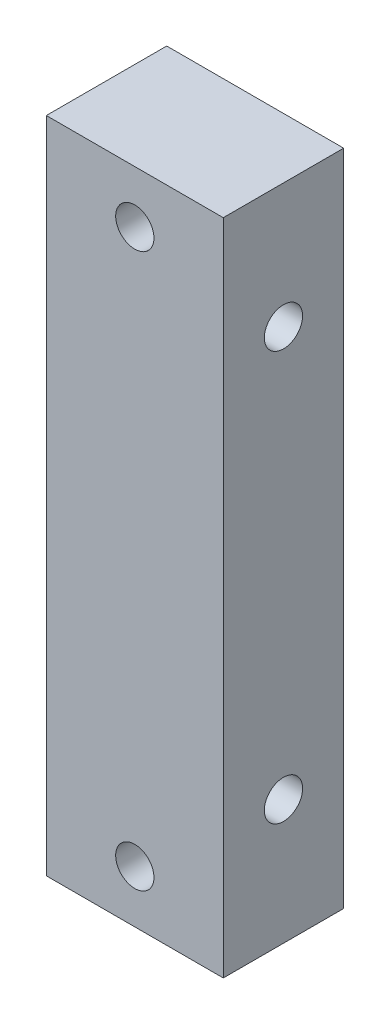
SolidWorks part; units mm, degrees
ref_plane "Front Plane" through (0, 0, 0) normal (0, 0, 1) x (1, 0, 0)
ref_plane "Top Plane" through (0, 0, 0) normal (0, 1, 0) x (1, 0, 0)
ref_plane "Right Plane" through (0, 0, 0) normal (1, 0, 0) x (0, 0, -1)
sketch "Sketch1" plane through (0, 0, 0) normal (0, 0, 1) x (1, 0, 0)
  line L1 (-9.3345, 34.7345) -> (9.3345, 34.7345)
  line L2 (-9.3345, 34.7345) -> (-9.3345, -34.7345)
  line L3 (-9.3345, -34.7345) -> (9.3345, -34.7345)
  line L4 (9.3345, 34.7345) -> (9.3345, -34.7345)
  line L5 (-9.3345, 34.7345) -> (9.3345, -34.7345) construction
  line L6 (-9.3345, -34.7345) -> (9.3345, 34.7345) construction
  point P0 (0, 0)
  dimension "D1" = 18.669
  dimension "D2" = 69.469
extrude "Boss-Extrude1" add sketch "Sketch1" along normal blind 12.7
sketch "Sketch2" plane through (9.3345, 0, 0) normal (1, 0, 0) x (0, 0, -1)
  line L0 (-6.35, 21.59) -> (-6.35, -21.59) construction
  line L1 (-12.7, -34.7345) -> (-12.7, 34.7345) construction
  line L2 (0, -34.7345) -> (0, 34.7345) construction
  point P2 (-6.35, 0)
  point P7 (0, 0)
  dimension "D1" = 6.35
  dimension "D2" = 43.18
hole_wizard "Tap Drill for #10-32 Tap1" positions "Sketch3" profile "Sketch4" hole size "#10-32" standard "ANSI Inch" end condition through all
sketch "Sketch3" plane through (9.3345, 0, 0) normal (1, 0, 0) x (0, 0, -1)
  point P0 (-6.35, 21.59)
  point P3 (-6.35, -21.59)
sketch "Sketch4" plane through (9.3345, 21.59, 6.35) normal (0, 1, 0) x (0, 0, -1)
  line L0 (0, 0) -> (0, 18.669)
  line L1 (0, 18.669) -> (2.0193, 18.669)
  line L2 (2.0193, 18.669) -> (2.0193, 0)
  line L5 (2.0193, 0) -> (0, 0)
  line L11 (0, -6.35) -> (0, 107.95) construction
  dimension "Thru Hole Dia." = 4.0386
  dimension "Thru Hole Depth" = 18.669
sketch "Sketch5" plane through (0, 0, 12.7) normal (0, 0, 1) x (1, 0, 0)
  line L0 (0, 29.21) -> (0, -29.21) construction
  point P3 (0, 0)
  dimension "D1" = 58.42
hole_wizard "Tap Drill for #10-32 Tap2" positions "Sketch6" profile "Sketch8" hole size "#10-32" standard "ANSI Inch"
sketch "Sketch6" plane through (0, 0, 12.7) normal (0, 0, 1) x (1, 0, 0)
  point P0 (0, 29.21)
  point P3 (0, -29.21)
sketch "Sketch8" plane through (0, 29.21, 12.7) normal (1, 0, 0) x (0, -1, 0)
  line L0 (0, 0) -> (0, 7.5633)
  line L1 (0, 7.5633) -> (2.0193, 6.35)
  line L2 (2.0193, 6.35) -> (2.0193, 0)
  line L5 (2.0193, 0) -> (0, 0)
  line L10 (0, 7.5633) -> (-2.0193, 6.35) construction
  line L11 (0, -6.35) -> (0, 107.95) construction
  dimension "Hole Dia." = 4.0386
  dimension "Hole Depth" = 6.35
  dimension "Drill Angle" = 118
